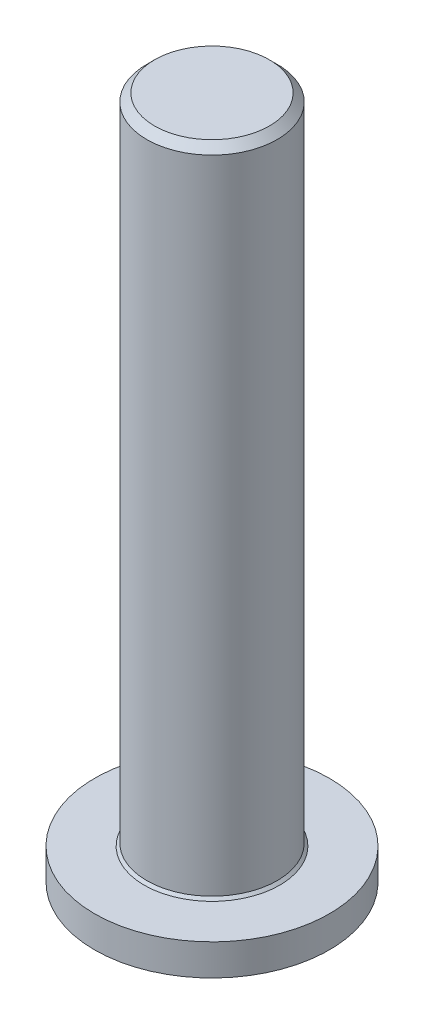
SolidWorks part; units mm, degrees
material "Alloy Steel"
ref_plane "Front Plane" through (0, 0, 0) normal (0, 0, 1) x (1, 0, 0)
ref_plane "Top Plane" through (0, 0, 0) normal (0, 1, 0) x (1, 0, 0)
ref_plane "Right Plane" through (0, 0, 0) normal (1, 0, 0) x (0, 0, -1)
sketch "Sketch2" plane through (0, 0, 0) normal (0, 1, 0) x (1, 0, 0)
  circle A0 centre (0, 0) radius 4.5
  dimension "D1" = 9
extrude "Boss-Extrude1" add sketch "Sketch2" along normal blind 1.5 contours A0
sketch "Sketch3" plane through (0, 1.5, 0) normal (0, 1, 0) x (1, 0, 0)
  circle A0 centre (0, 0) radius 2.5
  dimension "D1" = 5
extrude "Boss-Extrude2" add sketch "Sketch3" along normal blind 25
chamfer "Chamfer1" distance 0.1 angle 45 1 edges at (0, 1.5, 2.5)
chamfer "Chamfer2" distance 0.75 distance2 0.3 1 edges at (0, 0, 4.5) first distance on face at (0, 0, 4.5)
sketch "Sketch4" plane through (0, 0, 0) normal (0, -1, 0) x (1, 0, 0)
  line L1 (-0.4227, 1.6797) -> (-1.666, 0.4737)
  line L2 (-1.666, 0.4737) -> (-1.2433, -1.2059)
  line L3 (-1.2433, -1.2059) -> (0.4227, -1.6797)
  line L4 (0.4227, -1.6797) -> (1.666, -0.4737)
  line L5 (1.666, -0.4737) -> (1.2433, 1.2059)
  line L6 (1.2433, 1.2059) -> (-0.4227, 1.6797)
  circle A0 centre (0, 0) radius 1.5 construction
extrude "Cut-Extrude1" cut sketch "Sketch4" against normal blind 3
chamfer "Chamfer3" distance 0.3 angle 45 1 edges at (0, 26.5, 2.5)
ref_axis "Axis1" through (0, 24.7707, 0) along (0, -1, 0)
